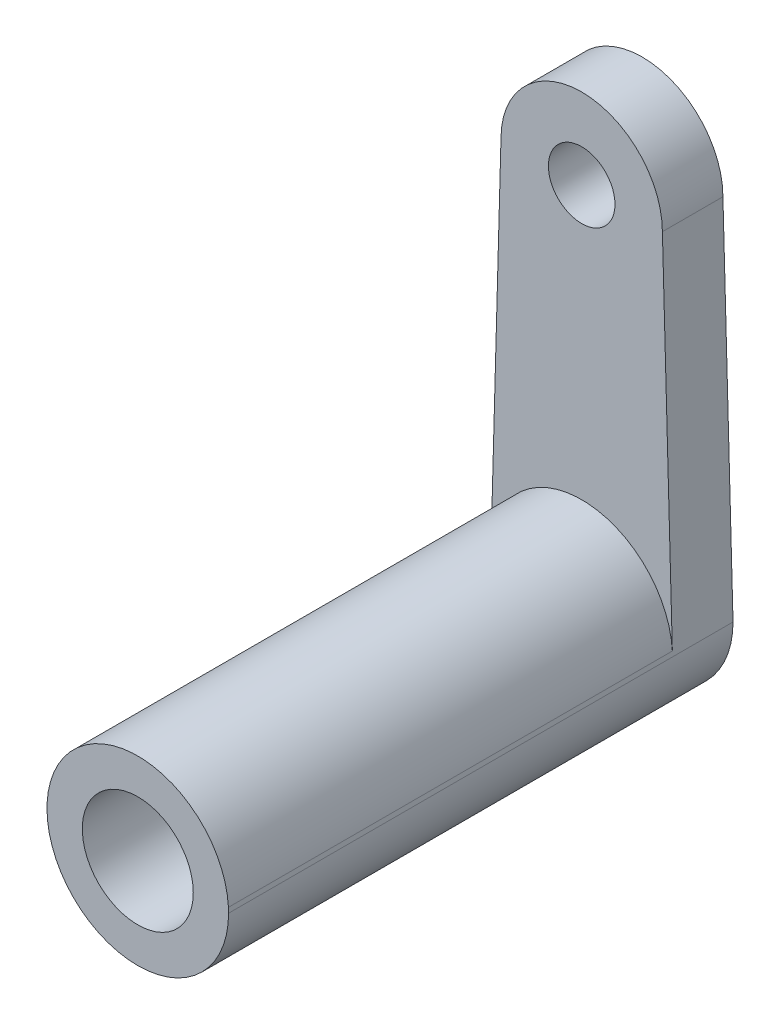
SolidWorks part; units mm, degrees
ref_plane "前视基准面" through (0, 0, 0) normal (0, 0, 1) x (1, 0, 0)
ref_plane "上视基准面" through (0, 0, 0) normal (0, 1, 0) x (1, 0, 0)
ref_plane "右视基准面" through (0, 0, 0) normal (1, 0, 0) x (0, 0, -1)
sketch "草图1" plane through (0, 0, 0) normal (0, 0, 1) x (1, 0, 0)
  line L0 (-1.8875, 2) -> (1.8875, 2)
  line L1 (0, -1000) -> (0, 49000) construction
  line L2 (-4, 18) -> (-4.5, 0)
  line L3 (4, 18) -> (4.5, 0)
  circle A0 centre (0, 0) radius 2.75
  circle A2 centre (0, 18) radius 1.65
  circle A3 centre (0, 0) radius 4.5
  circle A4 centre (0, 18) radius 4
  dimension "D1" = 5.5
  dimension "D3" = 18
  dimension "D4" = 3.3
  dimension "D5" = 9
  dimension "D6" = 8
  dimension "D2" = 2
extrude "凸台-拉伸3" add sketch "草图1" along normal blind 3 contours L1 A4 A2 | A4 L1 A2 | L1 A3 L3 A4 | A3 L1 A4 L2 | A3 L1 A0 L2 | L1 A3 L3 A0 | L1 L0 A0 | L0 L1 A0 region at (-0.7227, 2.3038, 0) region at (-2.6491, -1.0527, 0) region at (0.7227, 2.3038, 0) region at (0.1006, 3.625, 0) region at (-2.312, 9.1561, 0) region at (2.312, 9.1561, 0) region at (-1.9022, 18, 0) region at (1.9022, 18, 0)
extrude "凸台-拉伸5" add sketch "草图1<12>" along normal blind 25 contours L1 L0 A0 | L0 L1 A0 | A3 L1 A0 L2 | L1 A3 L3 A0 region at (-0.7227, 2.3038, 0) region at (-2.6491, -1.0527, 0) region at (0.7227, 2.3038, 0) region at (0.1006, 3.625, 0)
sketch "草图1<12>" plane through (0, 0, 0) normal (0, 0, 1) x (1, 0, 0) same geometry as "草图1"
extrude "切除-拉伸1" cut sketch "草图1<16>" against normal blind 10 from surface contours L1 A0 L0 | L1 L0 A0 | A0 L1 L0 | L0 L1 A0 region at (-0.7227, 2.3038, 0) region at (-1.2068, -0.2055, 0) region at (0.7227, 2.3038, 0) region at (1.2068, -0.2055, 0) starting at face at (0, -0.375, 25)
sketch "草图1<16>" plane through (0, 0, 0) normal (0, 0, 1) x (1, 0, 0) same geometry as "草图1"
